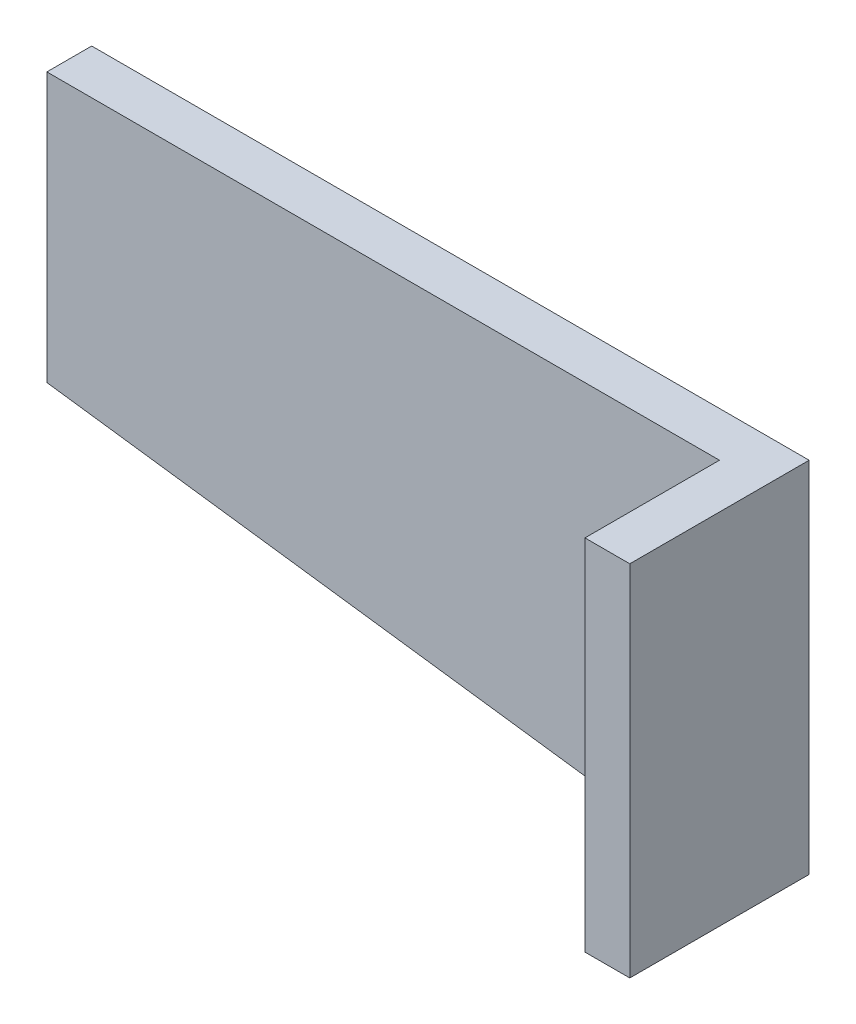
SolidWorks part; units mm, degrees
material "ABS"
ref_plane "Front Plane" through (0, 0, 0) normal (0, 0, 1) x (1, 0, 0)
ref_plane "Top Plane" through (0, 0, 0) normal (0, 1, 0) x (1, 0, 0)
ref_plane "Right Plane" through (0, 0, 0) normal (1, 0, 0) x (0, 0, -1)
sketch "Sketch2" plane through (0, 0, 0) normal (0, 0, 1) x (1, 0, 0)
  line L0 (0, 0) -> (50.8, 0)
  line L1 (50.8, 0) -> (50.8, -25.4)
  line L2 (50.8, -25.4) -> (47.625, -25.4)
  line L3 (47.625, -25.4) -> (0, -19.05)
  line L4 (0, -19.05) -> (0, 0)
  line L5 (47.625, -25.4) -> (47.625, 0)
  dimension "D1" = 3.175
  dimension "D2" = 19.05
  dimension "D3" = 50.8
  dimension "D4" = 25.4
extrude "Boss-Extrude1" add sketch "Sketch2" along normal blind 3.175 contours L3 L5 L0 L4 | L5 L2 L1 L0 region at (24.9464, -11.1881, 0) region at (49.2125, -12.7, 0)
extrude "Boss-Extrude2" add sketch "Sketch2<3>" along normal blind 12.7 contours L5 L2 L1 L0 region at (49.2125, -12.7, 0)
sketch "Sketch2<3>" plane through (0, 0, 0) normal (0, 0, 1) x (1, 0, 0) same geometry as "Sketch2"
